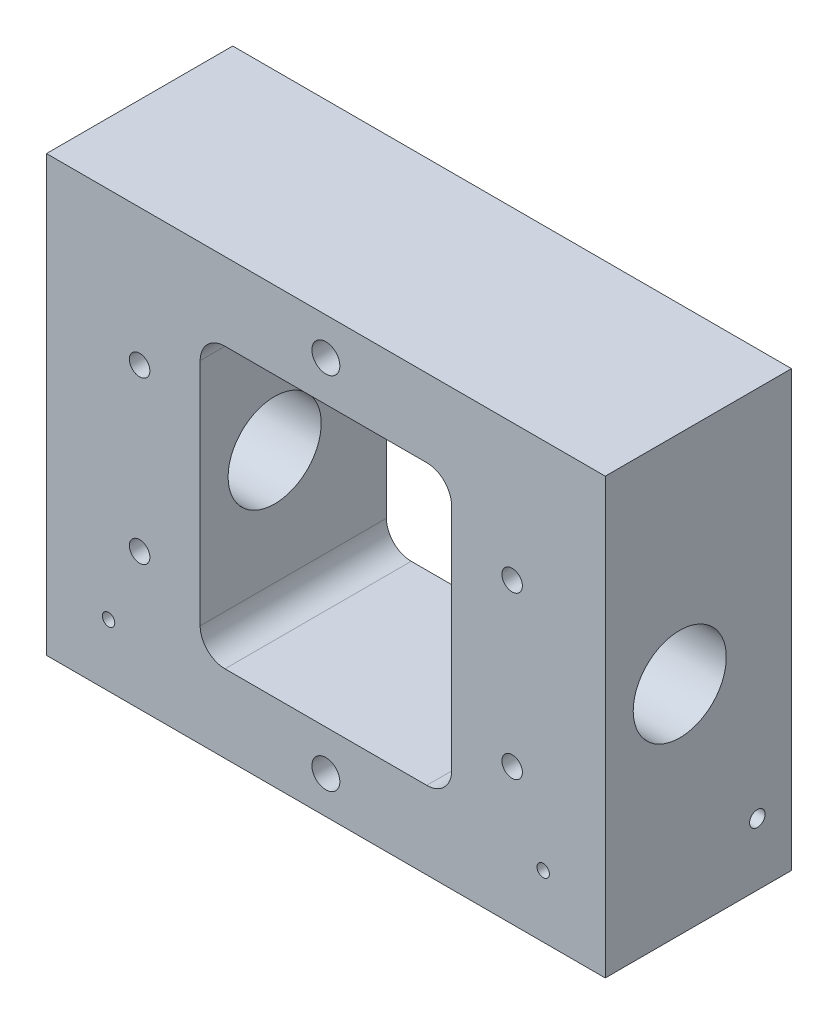
SolidWorks part; units mm, degrees
material "Lega 6061"
ref_plane "Piano frontale" through (0, 0, 0) normal (0, 0, 1) x (1, 0, 0)
ref_plane "Piano superiore" through (0, 0, 0) normal (0, 1, 0) x (1, 0, 0)
ref_plane "Piano destro" through (0, 0, 0) normal (1, 0, 0) x (0, 0, -1)
sketch "Schizzo1" plane through (0, 0, 0) normal (0, 0, 1) x (1, 0, 0)
  line L1 (0, 0) -> (90, 0)
  line L2 (0, 0) -> (0, 70)
  line L3 (0, 70) -> (90, 70)
  line L4 (90, 0) -> (90, 70)
  dimension "D1" = 90
  dimension "D2" = 70
extrude "Estrusione-Estrusione1" add sketch "Schizzo1" against normal blind 30
sketch "Schizzo2" plane through (0, 0, 0) normal (-1, 0, 0) x (0, 0, 1)
  line L0 (-30, 35) -> (0, 35) construction
  line L1 (-30, 70) -> (-30, 0) construction
  line L2 (0, 70) -> (0, 0) construction
  circle A0 centre (-12, 35) radius 7.5
  dimension "D1" = 15
  dimension "D2" = 18
extrude "Taglio-Estrusione1" cut sketch "Schizzo2" against normal through all
sketch "Schizzo3" plane through (0, 0, -30) normal (0, 0, -1) x (-1, 0, 0)
  line L0 (-94.314, 64) -> (4.9562, 64) construction
  line L2 (-90, 70) -> (0, 70) construction
  line L4 (-90, 35) -> (0, 35) construction
  line L5 (-90, 0) -> (-90, 70) construction
  line L6 (0, 70) -> (0, 0) construction
  line L7 (-94.314, 6) -> (4.9562, 6) construction
  line L8 (-45, 70) -> (-45, 0) construction
  line L9 (0, 0) -> (-90, 0) construction
  point P16 (-45, 64)
  point P17 (-45, 6)
  dimension "D1" = 6
hole_wizard "Foro lamato per Vite M4 a testa cilindrica piana-1" positions "Schizzo3D1" profile "Schizzo4" counterbore size "M4" standard "ISO" end condition through all
sketch3d "Schizzo3D1"
  line L0 (90, 70, -30) -> (0, 70, -30) construction
  point P0 (45, 64, -30)
  point P3 (45, 6, -30)
sketch "Schizzo4" plane through (45, 64, -30) normal (1, 0, 0) x (0, 1, 0)
  line L0 (0, 0) -> (0, 30)
  line L1 (0, 30) -> (2.25, 30)
  line L3 (2.25, 30) -> (2.25, 2.6)
  line L4 (2.25, 2.6) -> (4, 2.6)
  line L5 (4, 2.6) -> (4, 0)
  line L7 (4, 0) -> (0, 0)
  line L11 (0, -6.35) -> (0, 107.95) construction
  dimension "Thru Hole Dia." = 4.5
  dimension "Thru Hole Depth" = 30
  dimension "C'Bore Dia." = 8
  dimension "C'Bore Depth" = 2.6
ref_axis "Assi1" through (90, 35, -12) along (-1, 0, 0)
sketch "Schizzo14" plane through (0, 0, 0) normal (0, 0, 1) x (1, 0, 0)
  line L0 (45, 70) -> (45, 0) construction
  line L2 (61.25, 12.5) -> (28.75, 12.5)
  line L3 (65.25, 16.5) -> (65.25, 53.5)
  line L4 (90, 35) -> (0, 35) construction
  line L5 (61.25, 57.5) -> (28.75, 57.5)
  line L6 (24.75, 16.5) -> (24.75, 53.5)
  line L7 (65.25, 12.5) -> (24.75, 57.5) construction
  line L8 (65.25, 57.5) -> (24.75, 12.5) construction
  line L9 (0, 0) -> (90, 0) construction
  arc A0 (61.25, 57.5) -> (65.25, 53.5) centre (61.25, 53.5) cw
  arc A1 (65.25, 16.5) -> (61.25, 12.5) centre (61.25, 16.5) cw
  arc A2 (28.75, 12.5) -> (24.75, 16.5) centre (28.75, 16.5) cw
  arc A3 (24.75, 53.5) -> (28.75, 57.5) centre (28.75, 53.5) cw
  point P2 (45, 35)
  point P3 (45, 35)
  dimension "D1" = 4
  dimension "D2" = 45
  dimension "D3" = 40.5
  dimension "D4" = 12.5
extrude "Taglio-Estrusione4" cut sketch "Schizzo14" against normal through all
sketch "Schizzo16" plane through (0, 0, 0) normal (0, 0, 1) x (1, 0, 0)
  line L0 (45, 70) -> (45, 0) construction
  line L1 (0, 35) -> (90, 35) construction
  line L2 (0, 70) -> (0, 0) construction
  line L3 (0, 0) -> (90, 0) construction
  circle A0 centre (10, 10) radius 1
  circle A1 centre (80, 10) radius 1
  dimension "D1" = 2
  dimension "D2" = 10
  dimension "D3" = 10
  dimension "D4" = 35
  dimension "D5" = 25
extrude "Taglio-Estrusione6" cut sketch "Schizzo16" against normal through all
sketch "Schizzo17" plane through (0, 0, -30) normal (0, 0, -1) x (-1, 0, 0)
  line L0 (-45, 70) -> (-45, 0.5122) construction
  line L1 (-90, 70) -> (0, 70) construction
  line L2 (-45, 70) -> (-45, 0) construction
  line L3 (0, 35) -> (-90, 35) construction
  circle A0 centre (-10, 10) radius 8
  circle A1 centre (-80, 10) radius 8
  dimension "D1" = 16
extrude "Taglio-Estrusione8" cut sketch "Schizzo17" against normal blind 13
sketch "Schizzo18" plane through (0, 0, 0) normal (0, 0, 1) x (1, 0, 0)
  line L0 (0, 70) -> (90, 0) construction
  line L1 (90, 70) -> (0, 0) construction
  line L2 (45, 35) -> (45, 70) construction
  line L3 (15, 35.0996) -> (15, 74.2174) construction
  line L4 (24.75, 35) -> (0, 35) construction
  line L5 (24.75, 53.5) -> (24.75, 16.5) construction
  line L6 (90, 35) -> (0, 35) construction
  line L7 (90, 70) -> (0, 70) construction
  line L8 (45, 70) -> (45, 0) construction
  point P9 (15, 22)
  point P11 (45, 35)
  point P17 (15, 48)
  point P24 (75, 22)
  point P25 (75, 48)
  dimension "D1" = 13
  dimension "D2" = 30
hole_wizard "Foro filettato M4-1" positions "Schizzo20" profile "Schizzo19" tap size "M4" standard "ISO" end condition through all
sketch "Schizzo20" plane through (0, 0, 0) normal (0, 0, 1) x (1, 0, 0)
  point P0 (15, 48)
  point P3 (15, 22)
  point P6 (75, 48)
  point P9 (75, 22)
cosmetic thread "Filettatura del foro1" parameters "D2"=4
cosmetic thread "Filettatura del foro2" parameters "D2"=4
cosmetic thread "Filettatura del foro3" parameters "D2"=4
cosmetic thread "Filettatura del foro4" parameters "D2"=4
sketch "Schizzo19" plane through (15, 48, 0) normal (1, 0, 0) x (0, -1, 0)
  line L0 (0, 0) -> (0, 30)
  line L1 (0, 30) -> (1.65, 30)
  line L2 (1.65, 30) -> (1.65, 0)
  line L5 (1.65, 0) -> (0, 0)
  line L11 (0, -6.35) -> (0, 107.95) construction
  dimension "Thru Tap Drill Dia." = 3.3
  dimension "Thru Tap Drill Depth" = 30
sketch "Schizzo21" plane through (0, 0, -30) normal (0, 0, -1) x (-1, 0, 0)
  line L0 (-70, 73.919) -> (-70, -6.106) construction
  line L1 (-45, 70) -> (-45, 0) construction
  line L2 (-90, 70) -> (0, 0) construction
  line L3 (0, 70) -> (-90, 0) construction
  line L4 (-90, 35) -> (0, 35) construction
  line L5 (-20, 72.5272) -> (-20, -6.106) construction
  point P6 (-70, 54.4444)
  point P9 (-70, 15.5556)
  point P14 (-20, 54.4444)
  point P15 (-20, 15.5556)
  dimension "D1" = 25
  dimension "D2" = 25
hole_wizard "Foro filettato M3-1" positions "Schizzo23" profile "Schizzo22" tap size "M3" standard "ISO"
sketch "Schizzo23" plane through (0, 0, -30) normal (0, 0, -1) x (-1, 0, 0)
  point P0 (-70, 54.4444)
  point P3 (-70, 15.5556)
  point P6 (-20, 54.4444)
  point P9 (-20, 15.5556)
sketch "Schizzo22" plane through (70, 54.4444, -30) normal (1, 0, 0) x (0, 1, 0)
  line L0 (0, 0) -> (0, 12.7511)
  line L1 (0, 12.7511) -> (1.25, 12)
  line L2 (1.25, 12) -> (1.25, 0)
  line L5 (1.25, 0) -> (0, 0)
  line L10 (0, 12.7511) -> (-1.25, 12) construction
  line L11 (0, -6.35) -> (0, 107.95) construction
  dimension "Tap Drill Dia." = 2.5
  dimension "Tap Drill Depth" = 12
  dimension "Drill Angle" = 118
cosmetic thread "Filettatura del foro5" parameters "D1"=8, "D2"=3
cosmetic thread "Filettatura del foro6" parameters "D1"=8, "D2"=3
cosmetic thread "Filettatura del foro7" parameters "D1"=8, "D2"=3
cosmetic thread "Filettatura del foro8" parameters "D1"=8, "D2"=3
sketch "Schizzo24" plane through (0, 0, 0) normal (-1, 0, 0) x (0, 0, 1)
  line L0 (-17, 18) -> (-17, 2) construction
  line L1 (-17, 10) -> (-30, 10) construction
  point P6 (-24.5, 10)
  dimension "D1" = 7.5
hole_wizard "Foro filettato M3-2" positions "Schizzo26" profile "Schizzo27" tap size "M3" standard "ISO" end condition up to next
sketch "Schizzo26" plane through (0, 0, 0) normal (-1, 0, 0) x (0, 0, 1)
  point P0 (-24.5, 10)
sketch "Schizzo27" plane through (0, 10, -24.5) normal (0, 1, 0) x (0, 0, 1)
  line L0 (0, 0) -> (0, 2)
  line L1 (0, 2) -> (1.25, 2)
  line L2 (1.25, 2) -> (1.25, 0)
  line L5 (1.25, 0) -> (0, 0)
  line L11 (0, -6.35) -> (0, 107.95) construction
  dimension "Thru Tap Drill Dia." = 2.5
  dimension "Thru Tap Drill Depth" = 2
cosmetic thread "Filettatura del foro9" parameters "D2"=3
sketch "Schizzo28" plane through (0, 0, 0) normal (0, -1, 0) x (1, 0, 0)
  line L0 (2, -17) -> (18, -17) construction
  line L1 (10, -17) -> (10, -30) construction
  line L2 (94.314, -30) -> (-4.9562, -30) construction
  point P8 (10, -24.5)
  dimension "D1" = 7.5
hole_wizard "Foro filettato M3-3" positions "Schizzo30" profile "Schizzo31" tap size "M3" standard "ISO" end condition up to next
sketch "Schizzo30" plane through (0, 0, 0) normal (0, -1, 0) x (-1, 0, 0)
  point P0 (-10, 24.5)
sketch "Schizzo31" plane through (10, 0, -24.5) normal (1, 0, 0) x (0, 0, -1)
  line L0 (0, 0) -> (0, 2)
  line L1 (0, 2) -> (1.25, 2)
  line L2 (1.25, 2) -> (1.25, 0)
  line L5 (1.25, 0) -> (0, 0)
  line L11 (0, -6.35) -> (0, 107.95) construction
  dimension "Thru Tap Drill Dia." = 2.5
  dimension "Thru Tap Drill Depth" = 2
cosmetic thread "Filettatura del foro10" parameters "D2"=3
sketch "Schizzo32" plane through (0, 0, 0) normal (0, -1, 0) x (1, 0, 0)
  line L0 (72, -17) -> (88, -17) construction
  line L1 (72, -17) -> (88, -17) construction
  line L2 (80, -17) -> (80, -30) construction
  line L3 (94.314, -30) -> (-4.9562, -30) construction
  point P9 (80, -24.5)
  dimension "D1" = 7.5
hole_wizard "Foro filettato M3-4" positions "Schizzo34" profile "Schizzo35" tap size "M3" standard "ISO" end condition up to next
sketch "Schizzo34" plane through (0, 0, 0) normal (0, -1, 0) x (-1, 0, 0)
  point P0 (-80, 24.5)
sketch "Schizzo35" plane through (80, 0, -24.5) normal (1, 0, 0) x (0, 0, -1)
  line L0 (0, 0) -> (0, 2)
  line L1 (0, 2) -> (1.25, 2)
  line L2 (1.25, 2) -> (1.25, 0)
  line L5 (1.25, 0) -> (0, 0)
  line L11 (0, -6.35) -> (0, 107.95) construction
  dimension "Thru Tap Drill Dia." = 2.5
  dimension "Thru Tap Drill Depth" = 2
cosmetic thread "Filettatura del foro11" parameters "D2"=3
sketch "Schizzo36" plane through (90, 0, 0) normal (1, 0, 0) x (0, 0, -1)
  line L0 (17, 18) -> (17, 2) construction
  line L1 (17, 10) -> (30, 10) construction
  point P8 (24.5, 10)
hole_wizard "Foro filettato M3-5" positions "Schizzo38" profile "Schizzo37" tap size "M3" standard "ISO" end condition up to next
sketch "Schizzo38" plane through (90, 0, 0) normal (1, 0, 0) x (0, 0, -1)
  point P0 (24.5, 10)
cosmetic thread "Filettatura del foro12" parameters "D2"=3
sketch "Schizzo37" plane through (90, 10, -24.5) normal (0, 1, 0) x (0, 0, -1)
  line L0 (0, 0) -> (0, 2)
  line L1 (0, 2) -> (1.25, 2)
  line L2 (1.25, 2) -> (1.25, 0)
  line L5 (1.25, 0) -> (0, 0)
  line L11 (0, -6.35) -> (0, 107.95) construction
  dimension "Thru Tap Drill Dia." = 2.5
  dimension "Thru Tap Drill Depth" = 2
